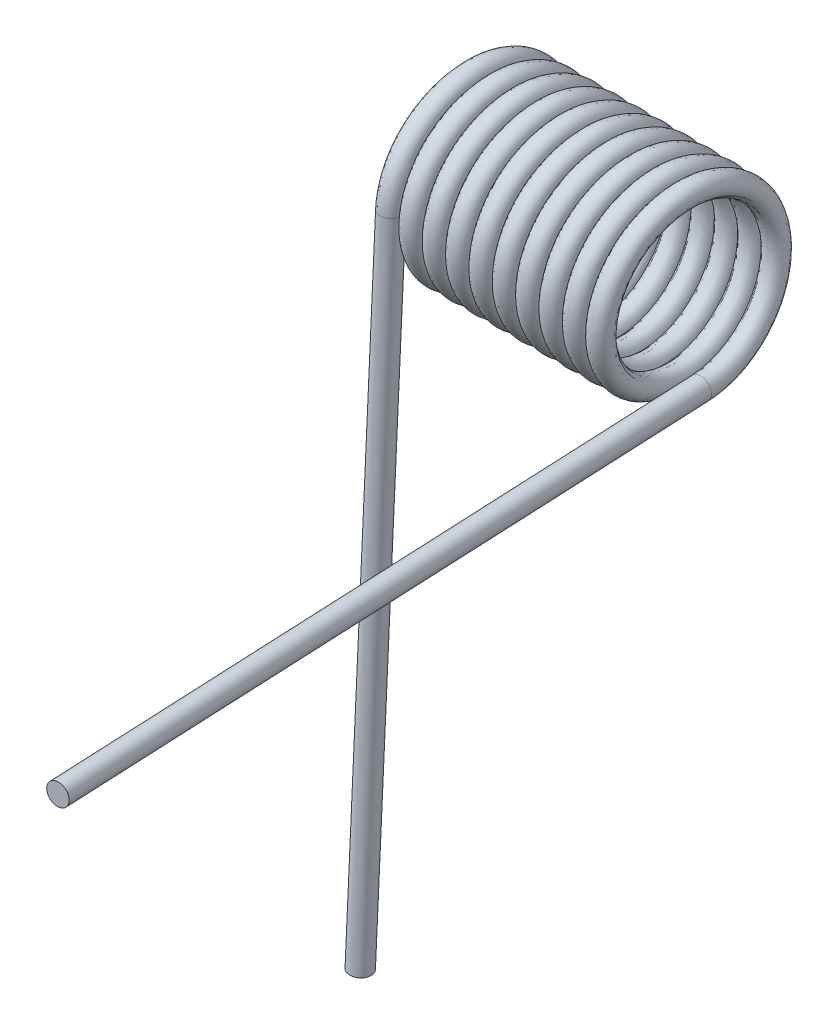
SolidWorks part; units mm, degrees
ref_plane "Front" through (0, 0, 0) normal (0, 0, 1) x (1, 0, 0)
ref_plane "Top" through (0, 0, 0) normal (0, 1, 0) x (1, 0, 0)
ref_plane "Right" through (0, 0, 0) normal (1, 0, 0) x (0, 0, -1)
sketch "Sketch1" plane through (0, 0, 0) normal (1, 0, 0) x (0, 0, -1)
  line L0 (0, -1.0033) -> (0, -1.3081) construction
  line L1 (-1.3081, 0) -> (-1.3081, -9.525) construction
  line L2 (0, -1.3081) -> (-9.525, -1.3081) construction
  line L3 (0, 0) -> (1.3081, 0) construction
  line L4 (0, 0) -> (-1.3081, 0) construction
  line L5 (-9.525, -1.3081) -> (-9.525, -1.0033) construction
  line L6 (-9.525, -1.0033) -> (0, -1.0033) construction
  line L7 (-1.3081, -9.525) -> (-1.0033, -9.525) construction
  line L8 (-1.0033, -9.525) -> (-1.0033, 0) construction
  circle A0 centre (0, 0) radius 1.3081 construction
  circle A1 centre (0, 0) radius 0.762 construction
  circle A2 centre (0, 0) radius 1.1557 construction
  point P7 (0, -1.1557)
  point P10 (0, 1.3081)
  dimension "OD" = 2.6162
  dimension "For Shaft Diameter" = 1.524
  dimension "Wire Diameter" = 0.3048
  dimension "Leg Length" = 9.525
  dimension "Deflection Angle" = 270
sketch "Sketch2" plane through (0, 0, 0) normal (1, 0, 0) x (0, 0, -1)
  circle A0 centre (0, 0) radius 1.1557 construction
  circle A2 centre (0, 0) radius 1.1557
curve "Helix/Spiral1" pitch 0.3302 height 3.2194 turns 9.75
ref_plane "Plane1" through (0, -1.1557, 0) normal (-0.0454, 0, -0.999) x (0.9987, -0.0232, -0.0454)
sketch "Sketch3" plane through (0, -1.1557, 0) normal (-0.0454, 0, -0.999) x (0.9987, -0.0232, -0.0454)
  circle A0 centre (0, 0) radius 0.1524
  dimension "D1" = 0.3048
sweep "Sweep1" add profiles "Sketch3" path "Helix/Spiral1"
sketch "Sketch4" plane through (0, 0, 0) normal (0.0454, 0, 0.999) x (-0.9987, 0.0232, 0.0454)
  circle A1 centre (-0.0269, 1.1554) radius 0.1524
  circle A2 centre (-0.0269, 1.1554) radius 0.1524
  dimension "D1" = 0
extrude "Extrude1" add sketch "Sketch4" along normal blind 9.525
sketch "Sketch5" plane through (-0.0066, -0.1461, 0) normal (-0.0454, -0.999, 0) x (0.9437, -0.0429, -0.3279)
  circle A1 centre (-3.4173, 0.0371) radius 0.1524
  circle A2 centre (-3.4173, 0.0371) radius 0.1524
  dimension "D1" = 0
extrude "Extrude2" add sketch "Sketch5" along normal blind 9.525
sketch "Sketch6" plane through (0, 0, 0) normal (1, 0, 0) x (0, 0, -1)
  circle A2 centre (0, 0) radius 1.0033 construction
equation "\"D4@Helix/Spiral1\" = \"Wire Diameter@Sketch1\" + .001"
equation "\"D1@Sketch3\"=\"Wire Diameter@Sketch1\""
equation "\"D1@Extrude2\"=\"Leg Length@Sketch1\""
equation "\"Leg Length@Extrude1\"=\"Leg Length@Sketch1\""
